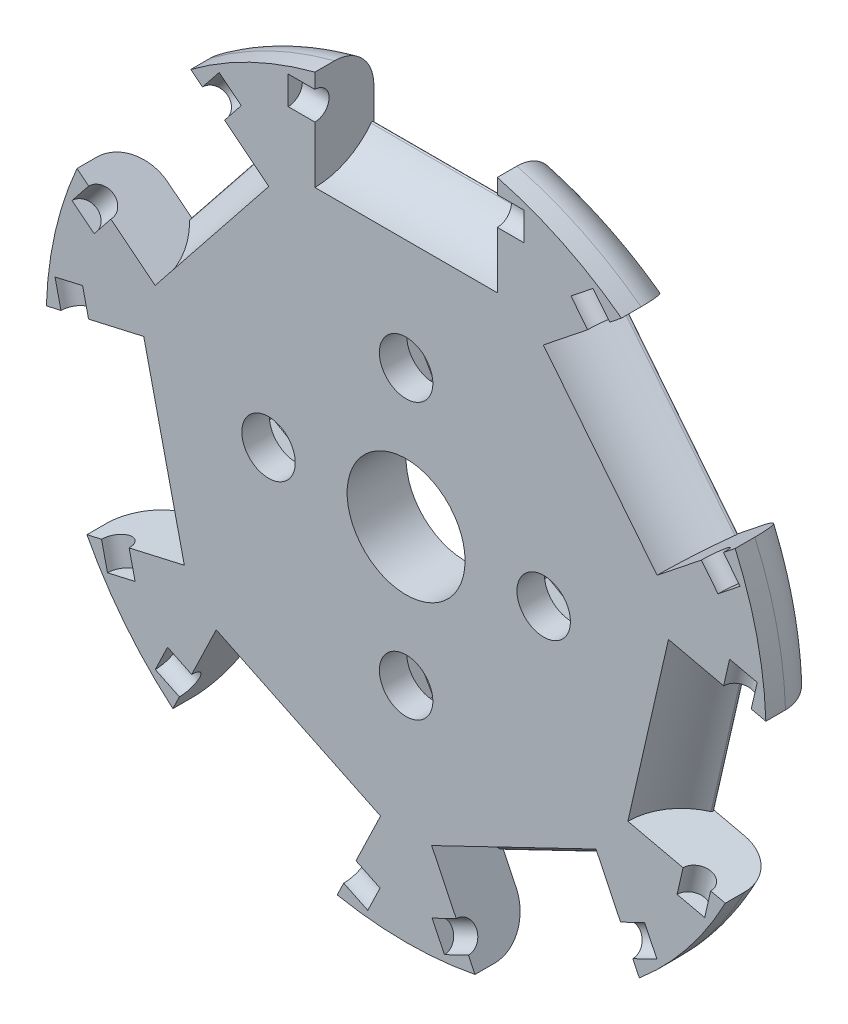
SolidWorks part; units mm, degrees
other "Markup1"
sketch "Sketch8" plane through (32.7336, 32.7336, 0) normal (0.5701, 0.1846, 0.8006) x (0.8043, 0.0736, -0.5897)
ref_plane "Front Plane" through (0, 0, 0) normal (0, 0, 1) x (1, 0, 0)
ref_plane "Top Plane" through (0, 0, 0) normal (0, 1, 0) x (1, 0, 0)
ref_plane "Right Plane" through (0, 0, 0) normal (1, 0, 0) x (0, 0, -1)
sketch "Sketch1" plane through (0, 0, 0) normal (0, 0, 1) x (1, 0, 0)
  circle A0 centre (0, 0) radius 29.0703
  dimension "D1" = 58.1406
extrude "Boss-Extrude2" add sketch "Sketch1" against normal blind 4.7625
fillet "Fillet1" radius 3.175 1 edges at (29.0703, 0, -4.7625)
sketch "Sketch2" plane through (0, 0, 0) normal (0, 0, 1) x (1, 0, 0)
  line L1 (-12.7, 29.0703) -> (12.7, 29.0703) construction
  line L2 (-7.366, 30.3403) -> (7.366, 30.3403)
  line L3 (-7.366, 30.3403) -> (-7.366, 19.9263)
  line L4 (-7.366, 19.9263) -> (7.366, 19.9263)
  line L5 (7.366, 30.3403) -> (7.366, 19.9263)
  line L6 (-7.366, 30.3403) -> (7.366, 19.9263) construction
  line L7 (-7.366, 19.9263) -> (7.366, 30.3403) construction
  line L35 (0, 0) -> (0, 29.0703) construction
  circle A1 centre (0, 0) radius 29.0703 construction
  point P10 (0, 25.1333)
  circle M7 centre (0, 0) radius 29.0703
  dimension "D1" = 14.732
  dimension "D2" = 10.414
  dimension "D3" = 1.27
  dimension "D4" = 25.4
extrude "Cut-Extrude2" cut sketch "Sketch2" against normal blind 12.7 contours L5 L3 L4 M7 | L3 L2 L5 L4 region at (0, 24.3457, 0)
pattern_circular "CirPattern1" count 7 over 360 about axis through (0, 0, 0) along (0, 0, 1) of "Cut-Extrude2"
ref_plane "Plane1" through (0, 0, 0) normal (1, 0, 0) x (0, 0, -1)
sketch "Sketch4" plane through (0, 0, 0) normal (1, 0, 0) x (0, 0, -1)
  line L0 (4.7625, 19.9263) -> (0, 19.9263) construction
  circle A0 centre (0, 25.7683) radius 1.143
  dimension "D1" = 2.286
  dimension "D2" = 5.842
extrude "Cut-Extrude4" cut sketch "Sketch4" against normal mid plane 19.05
pattern_circular "CirPattern2" count 7 over 360 about axis through (0, 0, 0) along (0, 0, 1) of "Cut-Extrude4"
sketch "Sketch5" plane through (0, 0, 0) normal (0, 0, 1) x (1, 0, 0)
  circle A0 centre (0, 0) radius 4.7625
  dimension "D1" = 9.525
sketch "Sketch6" plane through (0, 0, -4.7625) normal (0, 0, -1) x (-1, 0, 0)
  circle A1 centre (11.1125, 0) radius 2.159
  circle A4 centre (0, -11.1125) radius 2.159
  circle A5 centre (-11.1125, 0) radius 2.159
  circle A6 centre (0, 11.1125) radius 2.159
  point P12 (0, 0)
  dimension "D4" = 4.318
  dimension "D1" = 11.1125
  dimension "D2" = 4
extrude "Cut-Extrude7" cut sketch "Sketch6" against normal through all
sketch "Sketch10" plane through (7.366, 0, 0) normal (-1, 0, 0) x (0, 0, 1)
  line L0 (-4.7625, 24.8256) -> (-4.7625, 19.9263) construction
  line L1 (-4.7625, 19.9263) -> (0, 19.9263)
  line L2 (-4.7625, 19.9263) -> (-4.7625, 22.6092)
  line L4 (0, 19.9263) -> (0, 20.0533)
  arc A0 (-4.7625, 22.6092) -> (0, 20.0533) centre (0, 25.7683) ccw
  dimension "D1" = 11.43
  dimension "D2" = 4.7625
extrude "Boss-Extrude4" add sketch "Sketch10" along normal up to next
fillet "Fillet2" radius 0.127 1 edges at (0, 22.6092, -4.7625)
pattern_circular "CirPattern5" count 7 over 360 about axis through (0, 0, 0) along (0, 0, 1) of "Boss-Extrude4", "Fillet2"
extrude "Cut-Extrude9" cut sketch "Sketch5" against normal up to next
sketch "Sketch7" plane through (0, 0, -4.7625) normal (0, 0, -1) x (-1, 0, 0)
  line L0 (15.5575, -2.5663) -> (15.5575, 2.5663)
  line L1 (2.5663, 15.5575) -> (-2.5663, 15.5575)
  line L2 (-2.5663, 15.5575) -> (-5.1326, 11.1125)
  line L3 (-5.1326, 11.1125) -> (-2.5663, 6.6675)
  line L4 (-2.5663, 6.6675) -> (2.5663, 6.6675)
  line L5 (2.5663, 6.6675) -> (5.1326, 11.1125)
  line L6 (5.1326, 11.1125) -> (2.5663, 15.5575)
  line L7 (15.5575, 2.5663) -> (11.1125, 5.1326)
  line L8 (11.1125, 5.1326) -> (6.6675, 2.5663)
  line L9 (6.6675, 2.5663) -> (6.6675, -2.5663)
  line L10 (6.6675, -2.5663) -> (11.1125, -5.1326)
  line L11 (11.1125, -5.1326) -> (15.5575, -2.5663)
  line L12 (-2.5663, -15.5575) -> (2.5663, -15.5575)
  line L13 (2.5663, -15.5575) -> (5.1326, -11.1125)
  line L14 (5.1326, -11.1125) -> (2.5663, -6.6675)
  line L15 (2.5663, -6.6675) -> (-2.5663, -6.6675)
  line L16 (-2.5663, -6.6675) -> (-5.1326, -11.1125)
  line L17 (-5.1326, -11.1125) -> (-2.5663, -15.5575)
  line L18 (-15.5575, 2.5663) -> (-15.5575, -2.5663)
  line L19 (-15.5575, -2.5663) -> (-11.1125, -5.1326)
  line L20 (-11.1125, -5.1326) -> (-6.6675, -2.5663)
  line L21 (-6.6675, -2.5663) -> (-6.6675, 2.5663)
  line L22 (-6.6675, 2.5663) -> (-11.1125, 5.1326)
  line L23 (-11.1125, 5.1326) -> (-15.5575, 2.5663)
  circle A9 centre (0, 11.1125) radius 4.445 construction
  point P1 (6.5039, -16.7126)
  point P5 (0, 0)
  point P15 (0, 0)
  point P35 (0, 0)
  dimension "D1" = 8.89
  dimension "D2" = 11.1125
  dimension "D3" = 5.1326
  dimension "D4" = 4
extrude "Cut-Extrude8" cut sketch "Sketch7" against normal blind 2.54 and the other way through all
